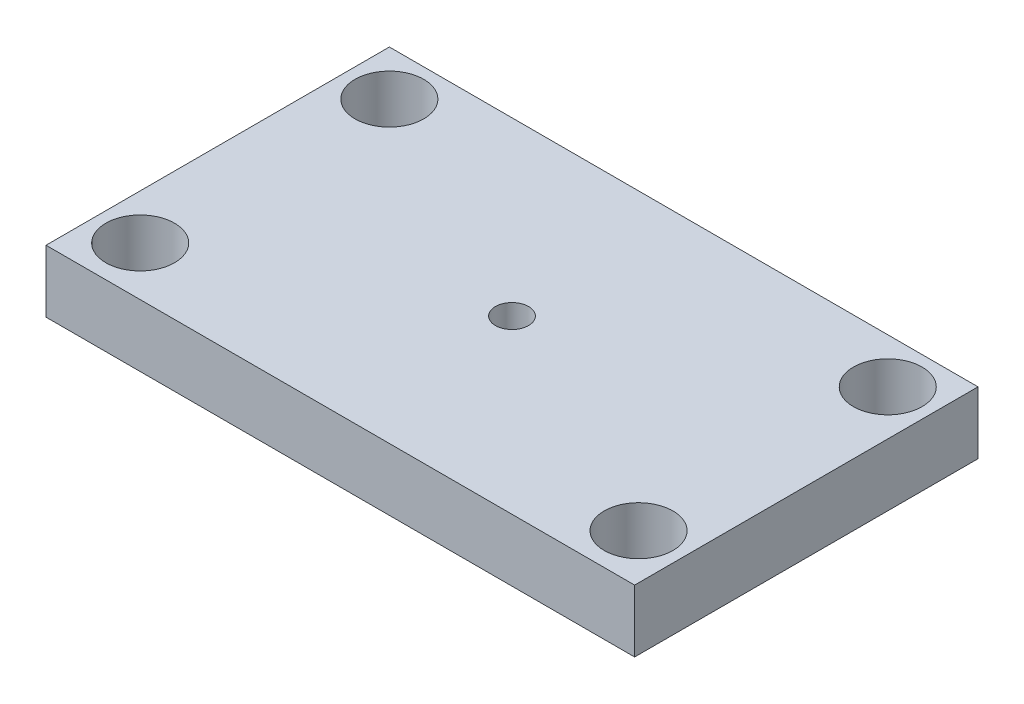
SolidWorks part; units mm, degrees
ref_plane "Front Plane" through (0, 0, 0) normal (0, 0, 1) x (1, 0, 0)
ref_plane "Top Plane" through (0, 0, 0) normal (0, 1, 0) x (1, 0, 0)
ref_plane "Right Plane" through (0, 0, 0) normal (1, 0, 0) x (0, 0, -1)
sketch "Sketch1" plane through (0, 0, 0) normal (0, 1, 0) x (1, 0, 0)
  line L0 (4.6, 30.4) -> (0, 30.4) construction
  line L1 (0, 0) -> (60, 0)
  line L2 (0, 0) -> (0, 35)
  line L3 (0, 35) -> (60, 35)
  line L4 (60, 0) -> (60, 35)
  line L5 (4.6, 30.4) -> (55.4, 30.4) construction
  line L6 (4.6, 30.4) -> (4.6, 5) construction
  line L7 (4.6, 5) -> (55.4, 5) construction
  line L8 (55.4, 30.4) -> (55.4, 5) construction
  line L9 (4.6, 30.4) -> (4.6, 35) construction
  circle A0 centre (4.6, 30.4) radius 3.5
  circle A1 centre (55.4, 30.4) radius 3.5
  circle A2 centre (4.6, 5) radius 3.5
  circle A3 centre (55.4, 5) radius 3.5
  circle A4 centre (30, 17.5) radius 1.6875
  point P13 (30, 30.4)
  point P14 (30, 35)
  point P20 (60, 17.5)
  dimension "D5" = 7
  dimension "D6" = 3.375
  dimension "D1" = 60
  dimension "D2" = 35
  dimension "D3" = 50.8
  dimension "D4" = 25.4
extrude "Boss-Extrude1" add sketch "Sketch1" along normal blind 6.35
